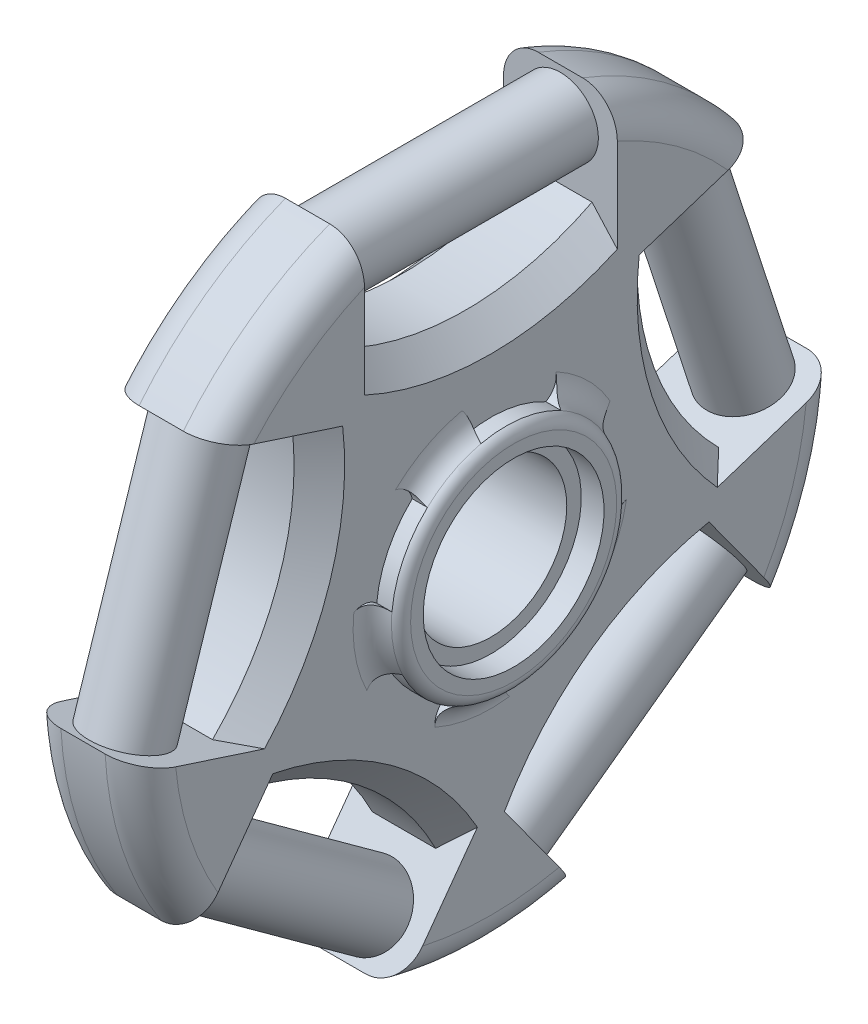
SolidWorks part; units mm, degrees
ref_plane "Front Plane" through (0, 0, 0) normal (0, 0, 1) x (1, 0, 0)
ref_plane "Top Plane" through (0, 0, 0) normal (0, 1, 0) x (1, 0, 0)
ref_plane "Right Plane" through (0, 0, 0) normal (1, 0, 0) x (0, 0, -1)
sketch "Sketch1" plane through (0, 0, 0) normal (1, 0, 0) x (0, 0, -1)
  line L0 (32.8598, 21.1914) -> (13.8386, 15.0111)
  line L1 (-10, 37.8) -> (10, 37.8)
  line L2 (-10, 37.8) -> (-10, 17.8)
  line L4 (10, 37.8) -> (10, 17.8)
  line L5 (-10, 37.8) -> (10, 17.8) construction
  line L6 (-10, 17.8) -> (10, 37.8) construction
  line L7 (39.0401, 2.1703) -> (20.019, -4.0101)
  line L8 (32.8598, 21.1914) -> (39.0401, 2.1703)
  line L9 (30.3085, -24.703) -> (18.5527, -8.5226)
  line L10 (14.1281, -36.4587) -> (2.3724, -20.2784)
  line L11 (30.3085, -24.703) -> (14.1281, -36.4587)
  line L12 (-14.1281, -36.4587) -> (-2.3724, -20.2784)
  line L13 (-30.3085, -24.703) -> (-18.5527, -8.5226)
  line L14 (-14.1281, -36.4587) -> (-30.3085, -24.703)
  line L15 (-39.0401, 2.1703) -> (-20.019, -4.0101)
  line L16 (-32.8598, 21.1914) -> (-13.8386, 15.0111)
  line L17 (-39.0401, 2.1703) -> (-32.8598, 21.1914)
  circle A0 centre (0, 0) radius 27.8
  arc A1 (-10, 17.8) -> (10, 17.8) centre (0, 37.3959) ccw
  arc A2 (13.8386, 15.0111) -> (20.019, -4.0101) centre (35.5656, 11.556) ccw
  arc A3 (18.5527, -8.5226) -> (2.3724, -20.2784) centre (21.9808, -30.2539) ccw
  arc A4 (-2.3724, -20.2784) -> (-18.5527, -8.5226) centre (-21.9808, -30.2539) ccw
  arc A5 (-20.019, -4.0101) -> (-13.8386, 15.0111) centre (-35.5656, 11.556) ccw
  circle A6 centre (0, 0) radius 6
  point P3 (0, 27.8)
  point P31 (0, 0)
  dimension "D1" = 55.6
  dimension "D4" = 22
  dimension "D6" = 12
  dimension "D2" = 20
  dimension "D3" = 20
  dimension "D5" = 5
extrude "Boss-Extrude2" add sketch "Sketch1" along normal blind 9 contours A5 L15 A0 L13 A4 L12 L10 A3 L9 L7 A2 L0 L4 A1 L2 L16 A6 region at (0, 17.0035, -17.4703)
fillet "Fillet1" radius 2.75 10 edges at (0, -8.5907, 26.4394) (9, -8.5907, 26.4394) (9, -27.8, 0) (0, -27.8, 0) (9, -8.5907, -26.4394) (0, -8.5907, -26.4394) (0, 22.4907, -16.3404) (9, 22.4907, -16.3404) (9, 22.4907, 16.3404) (0, 22.4907, 16.3404)
sketch "Sketch3" plane through (0, 0, 0) normal (-1, 0, 0) x (0, 0, 1)
  circle A0 centre (0, 0) radius 7.15
  circle A1 centre (0, 0) radius 9.15
  dimension "D1" = 14.3
  dimension "D2" = 18.3
extrude "Boss-Extrude3" add sketch "Sketch3" along normal blind 1.8 and the other way blind 10.8
chamfer "Chamfer2" distance 2 angle 45 10 edges at (9, -12.4556, -9.0495) (9, 4.7576, -14.6424) (9, -12.4556, 9.0495) (9, 4.7576, 14.6424) (9, 15.3959, 0) (0, 4.7576, 14.6424) (0, -12.4556, 9.0495) (0, -12.4556, -9.0495) (0, 4.7576, -14.6424) (0, 15.3959, 0)
fillet "Fillet3" radius 1 2 edges at (10.8, 0, 9.15) (-1.8, 0, 9.15)
fillet "Fillet4" radius 2 2 edges at (0, 0, -9.15) (9, 0, -9.15)
sketch "Sketch5" plane through (0, 0, 0) normal (-1, 0, 0) x (0, 0, 1)
  line L0 (6.2981, -6.5219) -> (7.5715, -7.8405) construction
  line L1 (0, 0) -> (4.168, -4.316) construction
  line L2 (0, 0) -> (6, 0) construction
  arc A0 (9.8091, -4.7521) -> (4.4069, -9.9689) centre (0, 0) cw
  circle A1 centre (0, 0) radius 10.8995 construction
  arc A2 (8.1947, -3.8793) -> (3.5909, -8.3251) centre (0, 0) cw
  circle A3 centre (0, 0) radius 9.0665 construction
  arc A4 (3.5909, -8.3251) -> (4.4069, -9.9689) centre (2.8248, -9.7298) cw
  arc A5 (8.1947, -3.8793) -> (9.8091, -4.7521) centre (8.3785, -5.4687) cw
  circle A6 centre (0, 0) radius 6 construction
  arc A7 (-1.1571, -8.9924) -> (-1.4883, -10.7975) centre (-2.6119, -9.6583) cw
  arc A8 (-1.4883, -10.7975) -> (-8.1192, -7.2717) centre (0, 0) cw
  arc A9 (-6.808, -5.9878) -> (-8.1192, -7.2717) centre (-8.3806, -5.6932) cw
  arc A10 (-1.1571, -8.9924) -> (-6.808, -5.9878) centre (0, 0) cw
  arc A11 (-8.9098, -1.6783) -> (-10.7289, -1.9211) centre (-9.9928, -0.5005) cw
  arc A12 (-10.7289, -1.9211) -> (-9.4248, 5.4747) centre (0, 0) cw
  arc A13 (-7.7985, 4.6244) -> (-9.4248, 5.4747) centre (-8.0044, 6.2111) cw
  arc A14 (-8.9098, -1.6783) -> (-7.7985, 4.6244) centre (0, 0) cw
  arc A15 (-4.3495, 7.9551) -> (-5.1425, 9.6101) centre (-3.5639, 9.349) cw
  arc A16 (-5.1425, 9.6101) -> (2.2944, 10.6553) centre (0, 0) cw
  arc A17 (1.9882, 8.8458) -> (2.2944, 10.6553) centre (3.4337, 9.5319) cw
  arc A18 (-4.3495, 7.9551) -> (1.9882, 8.8458) centre (0, 0) cw
  arc A19 (6.2217, 6.5949) -> (7.5507, 7.8605) centre (7.7901, 6.2785) cw
  arc A20 (7.5507, 7.8605) -> (10.8428, 1.1106) centre (0, 0) cw
  arc A21 (9.0273, 0.8426) -> (10.8428, 1.1106) centre (10.1265, -0.3201) cw
  arc A22 (6.2217, 6.5949) -> (9.0273, 0.8426) centre (0, 0) cw
  point P45 (0, 0)
  dimension "D2" = 1.6
  dimension "D1" = 46
  dimension "D3" = 7
  dimension "D4" = 6.4
  dimension "D5" = 5
extrude "Cut-Extrude1" cut sketch "Sketch5" along normal blind 1.8
ref_plane "Plane2" through (4.5, 0, 0) normal (1, 0, 0) x (0, 0, -1)
mirror "Mirror1" about plane through (4.5, 0, 0) normal (1, 0, 0) of "Cut-Extrude1"
sketch "Sketch6" plane through (0, -5.8779, -8.0902) normal (0, 0.5878, 0.809) x (1, 0, 0)
  line L3 (6.25, -25.9392) -> (2.75, -25.9392) construction
  line L4 (9, -22.9674) -> (9, -15.5785) construction
  circle A0 centre (4.5, -22.4392) radius 3
  dimension "D1" = 6
  dimension "D2" = 3.5
  dimension "D3" = 4.5
extrude "Boss-Extrude4" add sketch "Sketch6" along normal up to surface (20 mm away) up to face at (4.3028, -10.9073, 20.2853)
sketch "Sketch7" plane through (0, -9.5106, 3.0902) normal (0, 0.9511, -0.309) x (1, 0, 0)
  line L1 (6.25, -25.9392) -> (2.75, -25.9392) construction
  line L2 (0, -22.9674) -> (0, -15.5785) construction
  circle A0 centre (4.5, -22.4392) radius 3
  dimension "D1" = 6
  dimension "D2" = 3.5
  dimension "D3" = 4.5
extrude "Boss-Extrude5" add sketch "Sketch7" along normal up to surface (20 mm away) up to face at (4.3028, 15.9219, 16.6419)
sketch "Sketch8" plane through (0, 0, -10) normal (0, 0, 1) x (1, 0, 0)
  line L0 (9, 22.9674) -> (9, 15.5785) construction
  line L1 (6.25, 25.9392) -> (2.75, 25.9392) construction
  circle A0 centre (4.5, 22.4392) radius 3
  dimension "D1" = 6
  dimension "D2" = 4.5
  dimension "D3" = 3.5
extrude "Boss-Extrude6" add sketch "Sketch8" along normal up to surface (20 mm away) contours A0 up to face at (4.6972, 20.7476, 10)
sketch "Sketch9" plane through (0, -5.8779, 8.0902) normal (0, 0.5878, -0.809) x (-1, 0, 0)
  line L0 (-6.25, -25.9392) -> (-2.75, -25.9392) construction
  line L1 (-9, -22.9674) -> (-9, -15.5785) construction
  circle A0 centre (-4.5, -22.4392) radius 3
  dimension "D1" = 6
  dimension "D2" = 3.5
  dimension "D3" = 4.5
extrude "Boss-Extrude7" add sketch "Sketch9" along normal up to surface (20 mm away) up to face at (4.6972, -10.9073, -20.2853)
sketch "Sketch10" plane through (0, -9.5106, -3.0902) normal (0, 0.9511, 0.309) x (1, 0, 0)
  line L1 (6.25, 25.9392) -> (2.75, 25.9392) construction
  line L2 (9, 22.9674) -> (9, 15.5785) construction
  circle A0 centre (4.5, 22.4392) radius 3
  dimension "D1" = 6
  dimension "D2" = 3.5
  dimension "D3" = 4.5
extrude "Boss-Extrude8" add sketch "Sketch10" along normal up to surface (20 mm away) up to face at (4.6972, 15.9219, -16.6419)
scale "Scale2" scale about centroid uniform scaling yes scale factor 5
